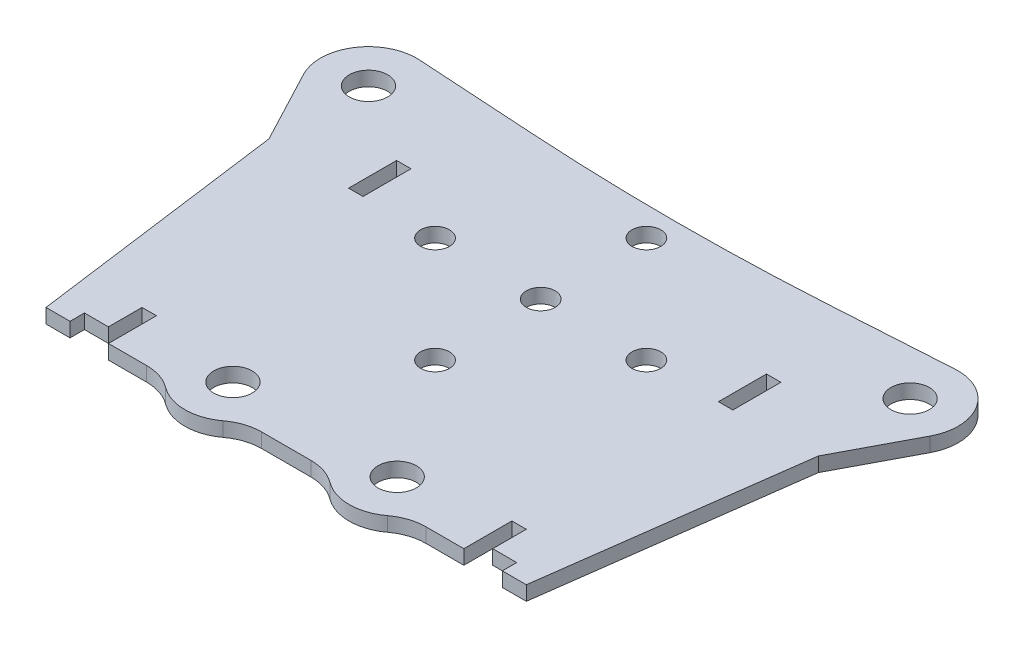
SolidWorks part; units mm, degrees
material "Stal węglowa"
ref_plane "Front" through (0, 0, 0) normal (0, 0, 1) x (1, 0, 0)
ref_plane "Top" through (0, 0, 0) normal (0, 1, 0) x (1, 0, 0)
ref_plane "Right" through (0, 0, 0) normal (1, 0, 0) x (0, 0, -1)
sketch "Szkic1" plane through (0, 0, 0) normal (0, 1, 0) x (1, 0, 0)
  line L36 (-50, -53) -> (-45, -53)
  line L37 (-37, -43) -> (-37, -53)
  line L38 (-45, -50) -> (-40, -50)
  line L39 (-45, -50) -> (-45, -53)
  line L40 (-40, -43) -> (-40, -50)
  line L41 (-40, -43) -> (-37, -43)
  line L42 (37, 10) -> (37, 0)
  line L43 (-37, 10) -> (-37, 0)
  line L44 (-40, 10) -> (-40, 0)
  line L45 (-40, 10) -> (-37, 10)
  line L46 (40, 10) -> (37, 10)
  line L47 (40, 0) -> (37, 0)
  line L48 (-40, 0) -> (-37, 0)
  line L49 (40, 10) -> (40, 0)
  line L50 (57.1882, 0.6181) -> (65.2263, 15.8553)
  line L51 (55.6412, 30.4938) -> (30.8739, 28.9615)
  line L52 (-57.1882, 0.6181) -> (-65.2263, 15.8553)
  line L53 (-55.6412, 30.4938) -> (-30.8739, 28.9615)
  line L54 (5.1215, -53) -> (-5.1215, -53)
  line L55 (45, -50) -> (45, -53)
  line L56 (37, -53) -> (29.0805, -53)
  line L57 (40, -43) -> (37, -43)
  line L58 (37, -43) -> (37, -53)
  line L59 (40, -43) -> (40, -50)
  line L60 (45, -50) -> (40, -50)
  line L61 (-37, -53) -> (-29.0805, -53)
  line L62 (50, -53) -> (45, -53)
  line L63 (-50, -53) -> (-57.1882, 0.6181)
  line L64 (50, -53) -> (57.1882, 0.6181)
  circle A11 centre (56.3816, 20.5212) radius 4
  circle A12 centre (0, 0) radius 3
  arc A13 (65.2263, 15.8553) -> (55.6412, 30.4938) centre (56.3816, 20.5212) ccw
  circle A14 centre (-56.3816, 20.5212) radius 4
  arc A15 (-55.6412, 30.4938) -> (-65.2263, 15.8553) centre (-56.3816, 20.5212) ccw
  arc A16 (-23.0907, -54.9923) -> (-11.1113, -54.9923) centre (-17.101, -46.9846) ccw
  circle A17 centre (-17.101, -46.9846) radius 4
  arc A18 (-5.1215, -53) -> (-11.1113, -54.9923) centre (-5.1215, -63) ccw
  circle A19 centre (0, 22) radius 3
  circle A20 centre (-22, 0) radius 3
  circle A21 centre (22, 0) radius 3
  circle A22 centre (0, -22) radius 3
  arc A23 (-30.8739, 28.9615) -> (30.8739, 28.9615) centre (0, 528.0074) ccw
  circle A24 centre (17.101, -46.9846) radius 4
  arc A25 (11.1113, -54.9923) -> (23.0907, -54.9923) centre (17.101, -46.9846) ccw
  arc A26 (29.0805, -53) -> (23.0907, -54.9923) centre (29.0805, -63) ccw
  arc A27 (11.1113, -54.9923) -> (5.1215, -53) centre (5.1215, -63) ccw
  arc A28 (-23.0907, -54.9923) -> (-29.0805, -53) centre (-29.0805, -63) ccw
extrude "Dodanie-wyciągnięcie1" add sketch "Szkic1" along normal blind 3
